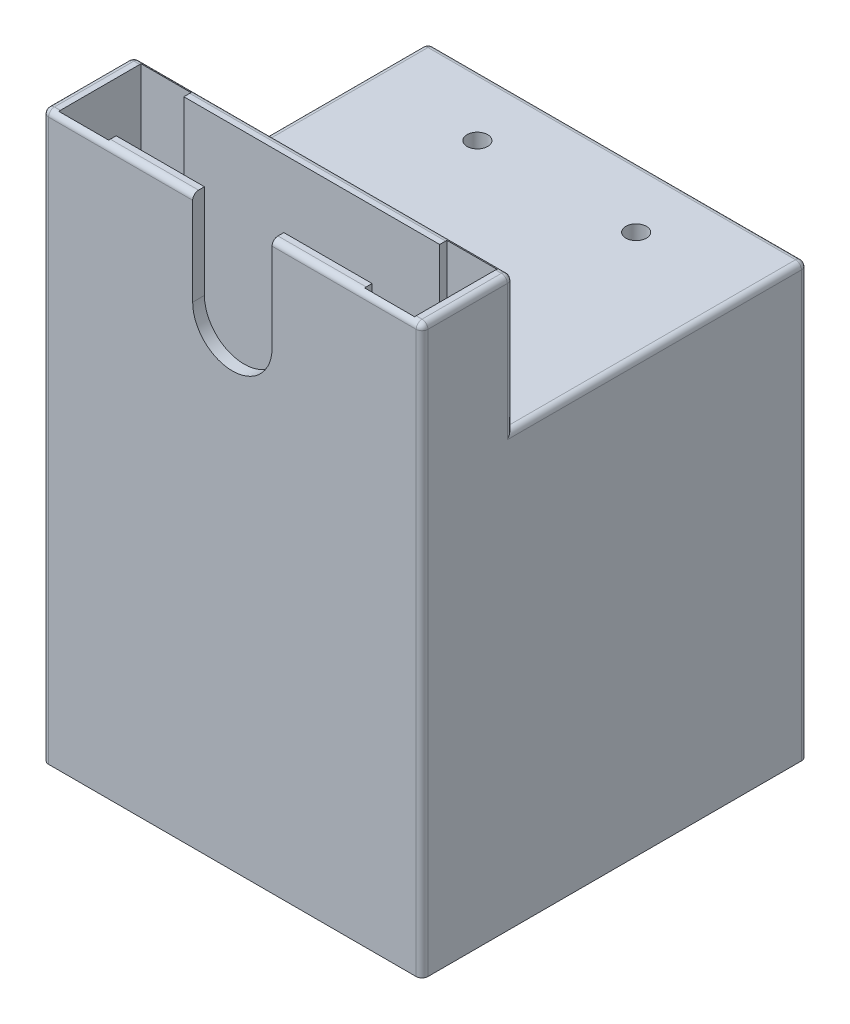
SolidWorks part; units mm, degrees
other "Markup3"
sketch "Sketch15" plane through (-20.4908, -10, -67.2849) normal (-0.1656, -0.0936, -0.9817) x (-0.9809, 0.1183, 0.1542)
ref_plane "Front Plane" through (0, 0, 0) normal (0, 0, 1) x (1, 0, 0)
ref_plane "Top Plane" through (0, 0, 0) normal (0, 1, 0) x (1, 0, 0)
ref_plane "Right Plane" through (0, 0, 0) normal (1, 0, 0) x (0, 0, -1)
sketch "Sketch2" plane through (0, 0, 0) normal (0, 1, 0) x (1, 0, 0)
  line L1 (-18.4908, 15.2849) -> (42.0092, 15.2849)
  line L2 (-18.4908, 15.2849) -> (-18.4908, 3.7849)
  line L3 (-18.4908, 3.7849) -> (42.0092, 3.7849)
  line L4 (42.0092, 15.2849) -> (42.0092, 3.7849)
  line L5 (-20.4908, 17.2849) -> (44.0092, 17.2849)
  line L6 (-20.4908, 17.2849) -> (-20.4908, 1.7849)
  line L7 (-20.4908, 1.7849) -> (44.0092, 1.7849)
  line L8 (44.0092, 17.2849) -> (44.0092, 1.7849)
  dimension "D1" = 60.5
  dimension "D2" = 11.5
  dimension "D3" = 2
  dimension "D4" = 2
  dimension "D5" = 2
  dimension "D6" = 2
extrude "Boss-Extrude3" add sketch "Sketch2" along normal blind 86.3
sketch "Sketch3" plane through (0, 0, 0) normal (0, 0, 1) x (1, 0, 0)
  line L0 (-20.4908, 86.3) -> (44.0092, 86.3) construction
  line L1 (5.0092, 86.3) -> (18.5092, 86.3)
  line L2 (5.0092, 86.3) -> (5.0092, 70.3)
  line L4 (18.5092, 86.3) -> (18.5092, 70.3)
  line L5 (44.0092, 86.3) -> (44.0092, 0) construction
  line L7 (-20.4908, 86.3) -> (-20.4908, 0) construction
  arc A1 (5.0092, 70.3) -> (18.5092, 70.3) centre (11.7592, 70.3) ccw
  dimension "D1" = 25.5
  dimension "D2" = 25.5
extrude "Cut-Extrude4" cut sketch "Sketch3" against normal blind 5.3
sketch "Sketch4" plane through (0, 0, -17.2849) normal (0, 0, -1) x (-1, 0, 0)
  line L0 (-44.0092, 86.3) -> (-44.0092, 0) construction
  line L1 (-44.0092, 63.3) -> (20.4908, 63.3)
  line L2 (-44.0092, 63.3) -> (-44.0092, 0)
  line L3 (-44.0092, 0) -> (20.4908, 0)
  line L4 (20.4908, 63.3) -> (20.4908, 0)
  line L5 (-44.0092, 86.3) -> (20.4908, 86.3) construction
  dimension "D1" = 23
extrude "Boss-Extrude4" add sketch "Sketch4" along normal blind 50 contours L2 L1 L4 L3
sketch "Sketch5" plane through (0, 0, 0) normal (0, -1, 0) x (-1, 0, 0)
  line L0 (20.4908, 1.7849) -> (-44.0092, 1.7849)
  line L1 (20.4908, 1.7849) -> (-44.0092, 1.7849) construction
  line L2 (-44.0092, 1.7849) -> (-44.0092, 67.2849)
  line L3 (-44.0092, 67.2849) -> (20.4908, 67.2849)
  line L4 (20.4908, 67.2849) -> (20.4908, 1.7849)
  line L5 (18.4908, 3.7849) -> (-42.0092, 3.7849)
  line L6 (-42.0092, 3.7849) -> (-42.0092, 67.2849)
  line L7 (18.4908, 3.7849) -> (18.4908, 67.2849)
  line L8 (18.4908, 67.2849) -> (20.4908, 67.2849)
  line L9 (-42.0092, 67.2849) -> (-44.0092, 67.2849)
  line M5 (20.4908, 1.7849) -> (20.4908, 67.2849)
  line M6 (20.4908, 67.2849) -> (-44.0092, 67.2849)
  line M7 (-44.0092, 67.2849) -> (-44.0092, 1.7849)
  line M8 (-44.0092, 1.7849) -> (20.4908, 1.7849)
  line M9 (18.4908, 15.2849) -> (18.4908, 3.7849)
  line M10 (18.4908, 3.7849) -> (-42.0092, 3.7849)
  line M11 (-42.0092, 3.7849) -> (-42.0092, 15.2849)
extrude "Boss-Extrude5" add sketch "Sketch5" along normal blind 10 contours L7 L6 L3 M9 M10 M11 M7 M8 M5 M6
sketch "Sketch7" plane through (0, 86.3, 0) normal (0, 1, 0) x (1, 0, 0)
  line L1 (-18.4908, 15.2849) -> (-9.9908, 15.2849)
  line L2 (-18.4908, 15.2849) -> (-18.4908, 16.5349)
  line L3 (-18.4908, 16.5349) -> (-9.9908, 16.5349)
  line L4 (-9.9908, 15.2849) -> (-9.9908, 16.5349)
  line L7 (42.0092, 16.5349) -> (33.5092, 16.5349)
  line L8 (33.5092, 15.2849) -> (33.5092, 16.5349)
  line L9 (42.0092, 15.2849) -> (33.5092, 15.2849)
  line L10 (42.0092, 15.2849) -> (42.0092, 16.5349)
  line L16 (42.0092, 3.7849) -> (42.0092, 2.5349)
  line L17 (42.0092, 3.7849) -> (33.5092, 3.7849)
  line L18 (33.5092, 3.7849) -> (33.5092, 2.5349)
  line L19 (42.0092, 2.5349) -> (33.5092, 2.5349)
  line L20 (-18.4908, 2.5349) -> (-9.9908, 2.5349)
  line L21 (-9.9908, 3.7849) -> (-9.9908, 2.5349)
  line L22 (-18.4908, 3.7849) -> (-9.9908, 3.7849)
  line L23 (-18.4908, 3.7849) -> (-18.4908, 2.5349)
extrude "Cut-Extrude6" cut sketch "Sketch7" against normal blind 75
sketch "Sketch8" plane through (0, 0, -67.2849) normal (0, 0, -1) x (-1, 0, 0)
  line L0 (-44.0092, 63.3) -> (20.4908, 63.3) construction
  line L1 (-42.0092, 60.3) -> (18.4908, 60.3)
  line L2 (-42.0092, 60.3) -> (-42.0092, 3)
  line L3 (-42.0092, 3) -> (18.4908, 3)
  line L4 (18.4908, 60.3) -> (18.4908, 3)
  line L5 (-42.0092, 0) -> (18.4908, 0) construction
  line L6 (20.4908, 63.3) -> (20.4908, -10) construction
  line L7 (-44.0092, 63.3) -> (-44.0092, -10) construction
  line L8 (18.4908, -10) -> (18.4908, 0) construction
  dimension "D1" = 3
  dimension "D2" = 3
  dimension "D3" = 2
  dimension "D4" = 2
  dimension "D5" = 2
extrude "Cut-Extrude7" cut sketch "Sketch8" against normal blind 48 contours L2 L1 L4 L3
sketch "Sketch9" plane through (0, 63.3, 0) normal (0, 1, 0) x (1, 0, 0)
  line L0 (44.0092, 17.2849) -> (-20.4908, 17.2849) construction
  line L7 (44.0092, 17.2849) -> (-20.4908, 17.2849) construction
  circle A0 centre (-1.5908, 56.7849) radius 1.75
  circle A1 centre (25.4092, 56.7849) radius 1.75
  circle A2 centre (25.4092, 25.7849) radius 1.75
  circle A3 centre (-1.5908, 25.7849) radius 1.75
  point P0 (0, 0)
  dimension "D5" = 3.5
  dimension "D6" = 3.5
  dimension "D7" = 3.5
  dimension "D4" = 3.5
  dimension "D1" = 27
  dimension "D2" = 31
  dimension "D3" = 8.5
  dimension "D8" = 27
  dimension "D9" = 8.5
  dimension "D10" = 31
extrude "Cut-Extrude8" cut sketch "Sketch9" against normal blind 8
fillet "Fillet2" radius 1 1 edges at (-20.4908, 86.3, -9.5349)
fillet "Fillet3" radius 1 2 edges at (44.0092, 63.3, -42.2849) (44.0092, 74.8, -17.2849)
fillet "Fillet4" radius 1 1 edges at (-20.4908, 63.3, -42.2849)
fillet "Fillet5" radius 1 5 edges at (44.0092, 26.15, -67.2849) (11.7592, 63.3, -67.2849) (43.7163, 63.0071, -67.2849) (-20.4908, 26.15, -67.2849) (-20.1979, 63.0071, -67.2849)
fillet "Fillet6" radius 1 10 edges at (37.7592, 86.3, -2.5349) (37.7592, 86.3, -16.5349) (44.0092, 86.3, -9.0349) (-14.2408, 86.3, -16.5349) (-20.4908, 73.8, -17.2849) (-20.1979, 86.0071, -17.2849) (11.7592, 86.3, -17.2849) (43.7163, 86.3, -16.992) (-20.1979, 63.0071, -17.2849) (31.2592, 86.3, -1.7849)
fillet "Fillet7" radius 1 4 edges at (-14.2408, 86.3, -2.5349) (-7.2408, 86.3, -1.7849) (-20.4908, 37.65, -1.7849) (-20.1979, 86.0071, -1.7849)
fillet "Fillet8" radius 1 2 edges at (44.0092, 37.65, -1.7849) (43.7163, 86.0071, -2.0778)
sketch "Sketch11" plane through (0, -10, 0) normal (0, -1, 0) x (1, 0, 0)
  line L0 (-18.4908, -3.7849) -> (-18.4908, -67.2849) construction
  line L1 (-18.4908, -7.2849) -> (-19.2408, -7.2849)
  line L2 (-18.4908, -7.2849) -> (-18.4908, -17.7849)
  line L3 (-18.4908, -17.7849) -> (-19.2408, -17.7849)
  line L4 (-19.2408, -7.2849) -> (-19.2408, -17.7849)
  line L5 (-18.4908, -3.7849) -> (42.0092, -3.7849) construction
  line L7 (42.0092, -17.7849) -> (42.7592, -17.7849)
  line L8 (42.7592, -7.2849) -> (42.7592, -17.7849)
  line L9 (42.0092, -7.2849) -> (42.7592, -7.2849)
  line L10 (42.0092, -7.2849) -> (42.0092, -17.7849)
  dimension "D1" = 3.5
  dimension "D2" = 10.5
  dimension "D3" = 0.75
extrude "Cut-Extrude11" cut sketch "Sketch11" against normal blind 18.5
sketch "Sketch14" plane through (0, 0, -15.2849) normal (0, 0, 1) x (1, 0, 0)
  line L0 (-18.4908, 11.3) -> (-9.9908, 11.3) construction
  line L1 (-18.4908, 0) -> (42.0092, 0)
  line L2 (-18.4908, 0) -> (-18.4908, 11.3)
  line L3 (-18.4908, 11.3) -> (42.0092, 11.3)
  line L4 (42.0092, 0) -> (42.0092, 11.3)
  line L5 (42.0092, 0) -> (-18.4908, 0) construction
  line L6 (42.0092, 8.5) -> (42.0092, 0) construction
  point P7 (42.0092, 0)
extrude "Cut-Extrude12" cut sketch "Sketch14" against normal blind 2.5
sketch "Sketch16" plane through (0, 0, -3.7849) normal (0, 0, -1) x (-1, 0, 0)
  line L0 (18.4908, 11.3) -> (18.4908, -10) construction
  line L1 (-42.0092, -10) -> (18.4908, -10)
  line L2 (-42.0092, -10) -> (-42.0092, 0)
  line L3 (-42.0092, 0) -> (18.4908, 0)
  line L4 (18.4908, -10) -> (18.4908, 0)
  dimension "D1" = 10
extrude "Boss-Extrude6" add sketch "Sketch16" along normal blind 2
sketch "Sketch17" plane through (0, 0, -7.2849) normal (0, 0, -1) x (-1, 0, 0)
  line L1 (19.2408, -10) -> (18.4908, -10)
  line L2 (19.2408, -10) -> (19.2408, 8.5)
  line L3 (19.2408, 8.5) -> (18.4908, 8.5)
  line L4 (18.4908, -10) -> (18.4908, 8.5)
extrude "Cut-Extrude14" cut sketch "Sketch17" against normal blind 1.5
sketch "Sketch18" plane through (0, 0, -7.2849) normal (0, 0, -1) x (-1, 0, 0)
  line L1 (-42.7592, 8.5) -> (-42.0092, 8.5)
  line L2 (-42.7592, 8.5) -> (-42.7592, -10)
  line L3 (-42.7592, -10) -> (-42.0092, -10)
  line L4 (-42.0092, 8.5) -> (-42.0092, -10)
extrude "Cut-Extrude15" cut sketch "Sketch18" against normal blind 1.5
